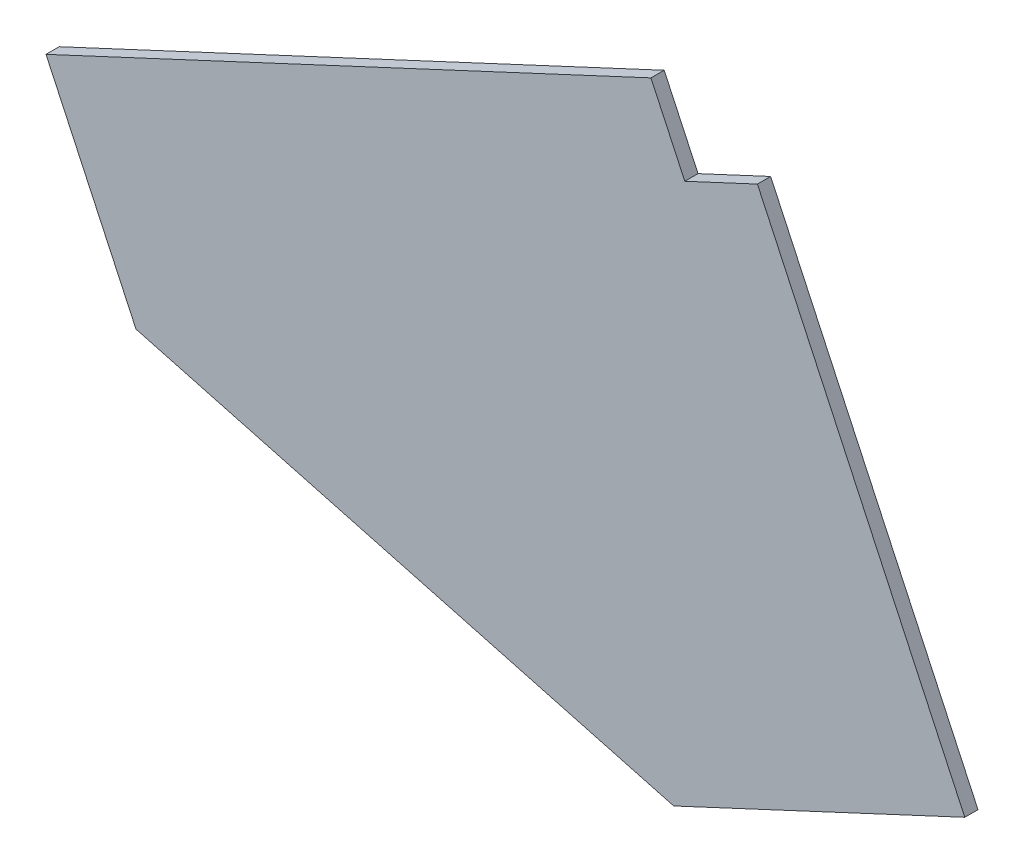
SolidWorks part; units mm, degrees
material "Balsa"
ref_plane "Front Plane" through (0, 0, 0) normal (0, 0, 1) x (1, 0, 0)
ref_plane "Top Plane" through (0, 0, 0) normal (0, 1, 0) x (1, 0, 0)
ref_plane "Right Plane" through (0, 0, 0) normal (1, 0, 0) x (0, 0, -1)
sketch "Sketch1" plane through (0, 0, 0) normal (0, 0, 1) x (1, 0, 0)
  line L0 (365.9798, -82.6535) -> (130.6366, -19.5934)
  line L1 (130.6366, -19.5934) -> (108.169, 28.5884)
  line L2 (108.169, 28.5884) -> (259.1989, 99.0148)
  line L3 (-63.4467, -51.4373) -> (255.5737, 97.3243) construction
  line L4 (259.1989, 99.0148) -> (267.6513, 80.8887)
  line L5 (267.6513, 80.8887) -> (285.7774, 89.341)
  line L6 (285.7774, 89.341) -> (365.9798, -82.6535)
  line L7 (327.4362, 0.0035) -> (398.701, -152.8244) construction
  line L10 (337.5482, -21.6817) -> (264.8848, -55.5651)
  line L12 (50.7481, 1.8126) -> (264.8848, -55.5651) construction
  line L15 (130.6366, -19.5934) -> (108.169, 28.5884) construction
  line L16 (309.1473, -45.959) -> (223.9543, -85.6851) construction
  point P19 (0, 0)
  point P20 (0, 0)
  dimension "D1" = 20
  dimension "D2" = 20
  dimension "D3" = 10
extrude "Boss-Extrude1" add sketch "Sketch1" against normal blind 3.3 contours L10 L6 L5 L4 L2 L1 L0 region at (229.671, 15.5188, 0)
